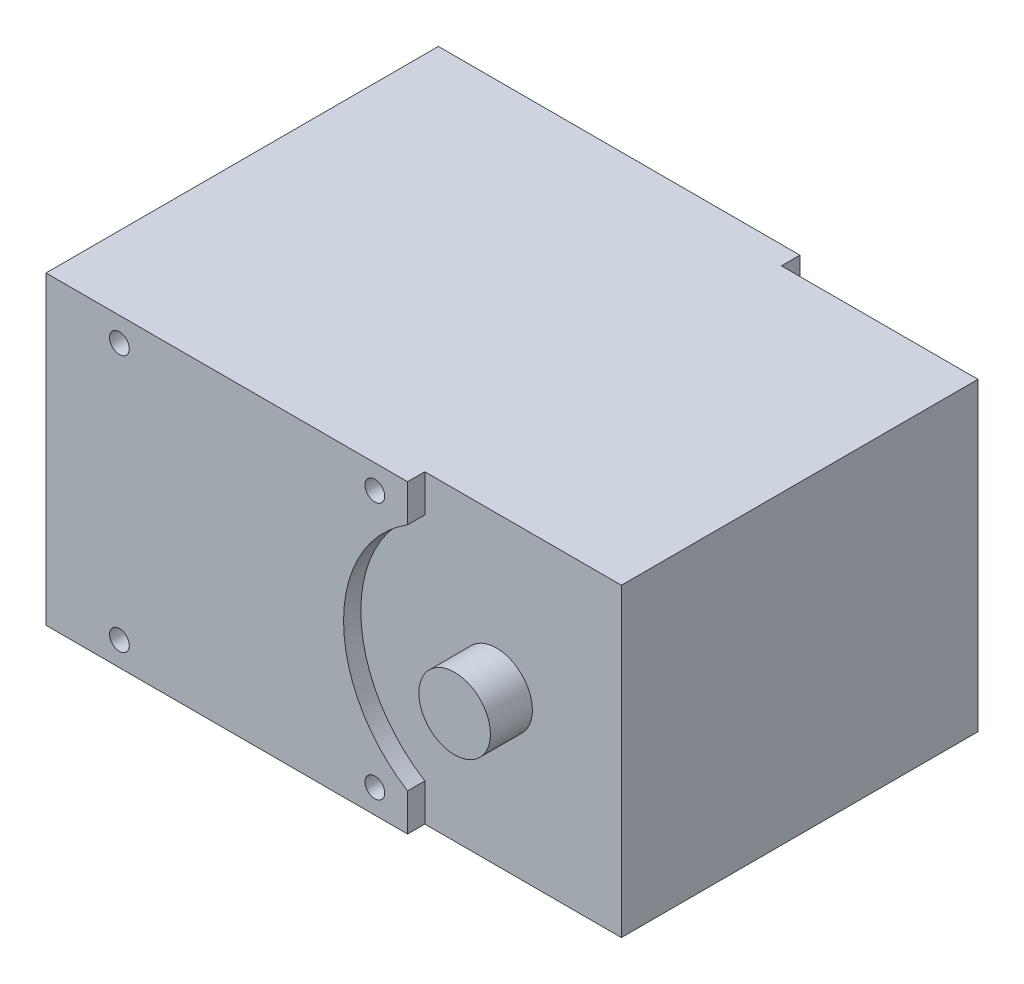
SolidWorks part; units mm, degrees
ref_plane "前视基准面" through (0, 0, 0) normal (0, 0, 1) x (1, 0, 0)
ref_plane "上视基准面" through (0, 0, 0) normal (0, 1, 0) x (1, 0, 0)
ref_plane "右视基准面" through (0, 0, 0) normal (1, 0, 0) x (0, 0, -1)
other "Configuration Table"
ref_axis "基准轴1" through (-88.99, 0, 0) along (1, 0, 0)
ref_axis "基准轴2" through (0, 66, 0) along (0, -1, 0)
ref_axis "基准轴3" through (0, 0, -88.99) along (0, 0, 1)
sketch "草图1" plane through (0, 0, 0) normal (0, 0, 1) x (1, 0, 0)
  line L1 (0, 0) -> (45.23, 0)
  line L2 (0, 0) -> (0, 24.73)
  line L3 (0, 24.73) -> (45.23, 24.73)
  line L4 (45.23, 0) -> (45.23, 24.73)
  dimension "D1" = 45.23
  dimension "D2" = 24.73
extrude "凸台-拉伸1" add sketch "草图1" along normal blind 28.9
sketch "草图2" plane through (0, 0, 28.9) normal (0, 0, 1) x (1, 0, 0)
  line L0 (0, 12.365) -> (45.23, 12.365) construction
  line L1 (0, 24.73) -> (0, 0) construction
  line L2 (45.23, 0) -> (45.23, 24.73) construction
  line L3 (22.615, 24.73) -> (22.615, 0) construction
  line L4 (45.23, 24.73) -> (0, 24.73) construction
  line L5 (0, 0) -> (45.23, 0) construction
  circle A0 centre (35.115, 12.365) radius 2.9
  dimension "D2" = 5.8
  dimension "D1" = 12.5
extrude "凸台-拉伸2" add sketch "草图2" along normal blind 3.4
sketch "草图3" plane through (0, 0, 28.9) normal (0, 0, 1) x (1, 0, 0)
  line L0 (29.3, 24.73) -> (29.3, 21.7023)
  line L1 (45.23, 24.73) -> (0, 24.73) construction
  line L2 (0, 0) -> (45.23, 0) construction
  line L3 (0, 24.73) -> (0, 0) construction
  line L4 (29.3, 3.0277) -> (29.3, 0)
  line L5 (29.3, 24.73) -> (0, 24.73)
  line L6 (0, 24.73) -> (0, 0)
  line L7 (0, 0) -> (29.3, 0)
  circle A0 centre (35.115, 12.365) radius 11 construction
  arc A1 (29.3, 21.7023) -> (29.3402, 3.0027) centre (35.115, 12.365) ccw
  line M4 (0, 24.73) -> (0, 0)
  line M5 (0, 0) -> (45.23, 0)
  line M7 (45.23, 24.73) -> (0, 24.73)
  dimension "D1" = 22
  dimension "D2" = 29.3
extrude "凸台-拉伸3" add sketch "草图3" along normal blind 1.4 contours A1 L0 L4 M7 M4 M5 region at (13.3447, 12.365, 28.9)
sketch "草图4" plane through (0, 0, 30.3) normal (0, 0, 1) x (1, 0, 0)
  line L0 (0, 12.365) -> (45.23, 12.365) construction
  line L1 (0, 24.73) -> (0, 0) construction
  line L2 (45.23, 0) -> (45.23, 24.73) construction
  line L3 (29.3, 24.73) -> (0, 24.73) construction
  line L4 (5.95, 22.78) -> (26.65, 22.78) construction
  line L5 (5.95, 1.95) -> (26.65, 1.95) construction
  circle A0 centre (5.95, 22.78) radius 0.8
  circle A1 centre (26.65, 22.78) radius 0.8
  circle A2 centre (26.65, 1.95) radius 0.8
  circle A3 centre (5.95, 1.95) radius 0.8
  dimension "D2" = 1.6
  dimension "D3" = 20.7
  dimension "D4" = 1.95
  dimension "D5" = 26.65
  dimension "D1" = 5.95
extrude "切除-拉伸1" cut sketch "草图4" against normal blind 5
sketch "草图6" plane through (0, 0, 0) normal (0, 0, -1) x (-1, 0, 0)
  line L0 (-29.3, 24.73) -> (-29.3, 21.7023) construction
  line L1 (-45.23, 12.365) -> (0, 12.365) construction
  line L2 (0, 24.73) -> (0, 0) construction
  line L3 (0, 0) -> (-29.3, 0) construction
  line L4 (-29.3, 3.0277) -> (-29.3, 0) construction
  line L5 (-29.3, 24.73) -> (-29.3, 21.7023)
  line L6 (-29.3, 24.73) -> (0, 24.73)
  line L7 (0, 24.73) -> (0, 0)
  line L8 (0, 0) -> (-29.3, 0)
  line L9 (-29.3, 3.0277) -> (-29.3, 0)
  line L10 (-2.27, 22.615) -> (-2.27, 2.115) construction
  line L11 (-26.71, 22.615) -> (-2.27, 22.615) construction
  line L12 (-26.71, 2.115) -> (-2.27, 2.115) construction
  line L13 (-45.23, 24.73) -> (0, 24.73) construction
  line L14 (-45.23, 0) -> (-45.23, 24.73) construction
  arc A0 (-29.3402, 3.0027) -> (-29.3, 21.7023) centre (-35.115, 12.365) ccw construction
  arc A1 (-29.3402, 3.0027) -> (-29.3, 21.7023) centre (-35.115, 12.365) ccw
  circle A2 centre (-2.27, 22.615) radius 0.8
  circle A3 centre (-2.27, 2.115) radius 0.8
  circle A6 centre (-26.71, 2.115) radius 0.8
  circle A8 centre (-26.71, 22.615) radius 0.8
  dimension "D1" = 2.27
  dimension "D3" = 20.5
  dimension "D5" = 1.6
  dimension "D6" = 26.71
  dimension "D2" = 26.71
  dimension "D7" = 24.44
extrude "切除-拉伸2" cut sketch "草图6" against normal blind 4.1 contours A8 | A2 | A3 | A6 region at (2.27, 22.615, 0) region at (2.27, 2.115, 0) region at (26.71, 22.615, 0)
sketch "草图7" plane through (0, 0, 0) normal (0, 0, -1) x (-1, 0, 0)
  line L0 (-29.3, 24.73) -> (-29.3, 21.7023) construction
  line L1 (-29.3, 24.73) -> (0, 24.73) construction
  line L2 (0, 24.73) -> (0, 0) construction
  line L3 (0, 0) -> (-29.3, 0) construction
  line L4 (-29.3, 3.0277) -> (-29.3, 0) construction
  line L5 (-29.3, 24.73) -> (-29.3, 21.7023)
  line L6 (-29.3, 24.73) -> (0, 24.73)
  line L7 (0, 24.73) -> (0, 0)
  line L8 (0, 0) -> (-29.3, 0)
  line L9 (-29.3, 3.0277) -> (-29.3, 0)
  arc A0 (-29.3402, 3.0027) -> (-29.3, 21.7023) centre (-35.115, 12.365) ccw construction
  circle A1 centre (-26.71, 2.115) radius 0.8
  circle A2 centre (-26.71, 2.115) radius 0.8
  circle A3 centre (-2.27, 2.115) radius 0.8
  circle A4 centre (-2.27, 2.115) radius 0.8
  circle A5 centre (-2.27, 22.615) radius 0.8
  circle A6 centre (-2.27, 22.615) radius 0.8
  circle A7 centre (-26.71, 22.615) radius 0.8
  circle A8 centre (-26.71, 22.615) radius 0.8
  arc A9 (-29.3402, 3.0027) -> (-29.3, 21.7023) centre (-35.115, 12.365) ccw
  circle M5 centre (-26.71, 2.115) radius 0.8
  circle M6 centre (-2.27, 2.115) radius 0.8
  circle M7 centre (-2.27, 22.615) radius 0.8
  circle M8 centre (-26.71, 22.615) radius 0.8
  line M10 (0, 0) -> (0, 24.73)
  line M11 (0, 24.73) -> (-45.23, 24.73)
  line M13 (-45.23, 0) -> (0, 0)
  dimension "D1" = 0
  dimension "D2" = 0
  dimension "D3" = 0
  dimension "D4" = 0
extrude "凸台-拉伸5" add sketch "草图7" along normal blind 1.5 contours A9 L9 L5 M13 M10 M11 M6 M8 M7 M5 region at (13.3305, 12.365, 0)
sketch "草图10" plane through (0, 0, 0) normal (0, 1, 0) x (1, 0, 0)
  line L0 (5.2, 1.5) -> (5.2, 3.5)
  line L1 (0, 1.5) -> (29.3, 1.5) construction
  line L2 (5.2, 3.5) -> (16.6, 3.5)
  line L3 (16.6, 3.5) -> (18.6, 1.5)
  line L4 (0, -30.3) -> (0, 1.5) construction
  line L5 (5.2, 1.5) -> (18.6, 1.5)
  dimension "D1" = 18.6
  dimension "D2" = 2
  dimension "D3" = 5.2
  dimension "D4" = 45
extrude "凸台-拉伸6" add sketch "草图10" along normal through all
sketch "草图5" plane through (0, 0, 0) normal (0, 0, -1) x (-1, 0, 0)
  circle A1 centre (-35.115, 12.365) radius 2.9
  circle A2 centre (-35.115, 12.365) radius 2.9
  dimension "D1" = 0
extrude "凸台-拉伸4" add sketch "草图5" along normal up to surface (3.5 mm away) up to face at (10.9, 12.365, -3.5)
sketch "草图11" plane through (0, 0, -1.5) normal (0, 0, -1) x (-1, 0, 0)
  line L0 (0, 12.365) -> (-45.23, 12.365) construction
  line L1 (-19.7364, 3.115) -> (0, 3.115)
  line L2 (-19.7364, 3.115) -> (-19.7364, 21.615)
  line L3 (-19.7364, 21.615) -> (0, 21.615)
  line L4 (0, 3.115) -> (0, 21.615)
  line L5 (-19.7364, 3.115) -> (0, 21.615) construction
  line L6 (-19.7364, 21.615) -> (0, 3.115) construction
  line L7 (0, 0) -> (0, 24.73) construction
  point P0 (-9.8682, 12.365)
  dimension "D1" = 18.5
extrude "切除-拉伸-薄壁1" cut sketch "草图11" along normal through all thin thin type one direction wall 10
